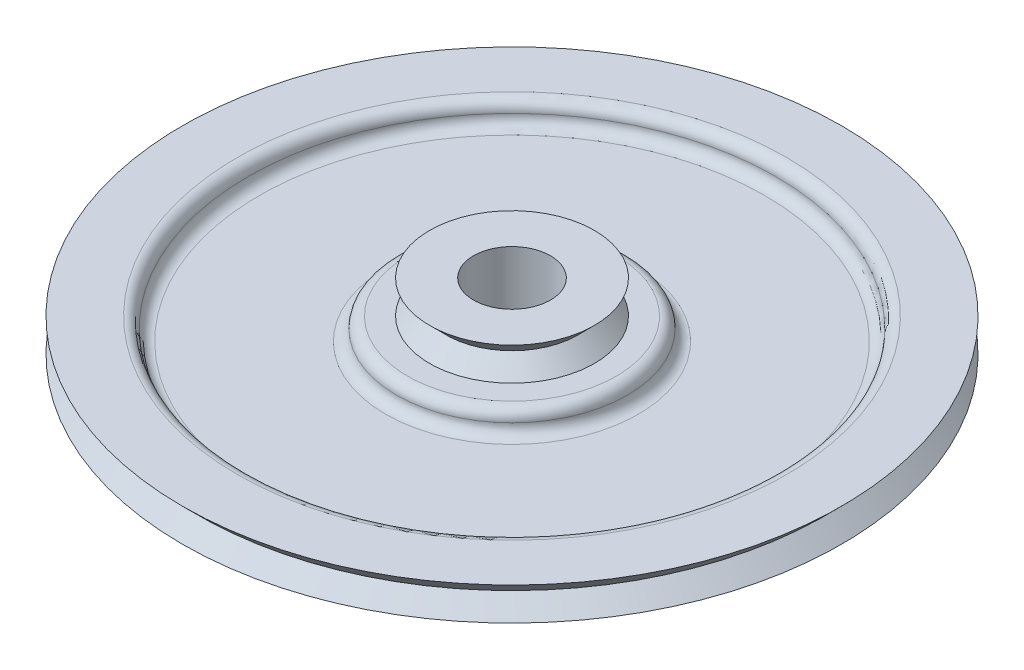
SolidWorks part; units mm, degrees
ref_plane "Front Plane" through (0, 0, 0) normal (0, 0, 1) x (1, 0, 0)
ref_plane "Top Plane" through (0, 0, 0) normal (0, 1, 0) x (1, 0, 0)
ref_plane "Right Plane" through (0, 0, 0) normal (1, 0, 0) x (0, 0, -1)
sketch "Sketch1" plane through (0, 0, 0) normal (0, 0, 1) x (1, 0, 0)
  line L0 (0, 0) -> (0, 13.2622) construction
  line L1 (-3.5, 6) -> (-3.5, 0)
  line L2 (-3.5, 0) -> (-30, 0)
  line L3 (-30, 0) -> (-28.5, 1.5)
  line L4 (-28.5, 1.5) -> (-30, 3)
  line L5 (-30, 3) -> (-7.5, 3)
  line L6 (-7.5, 3) -> (-6, 4.5)
  line L7 (-6, 4.5) -> (-7.5, 6)
  line L8 (-7.5, 6) -> (-3.5, 6)
  point P3 (0, 0)
  dimension "D1" = 3
  dimension "D2" = 7
  dimension "D3" = 15
  dimension "D4" = 60
  dimension "D5" = 45
revolve "Revolve1" add sketch "Sketch1" angle 360 about L0
sketch "Sketch2" plane through (0, 3, 0) normal (0, 1, 0) x (1, 0, 0)
  circle A0 centre (0, 0) radius 10.5
  circle A1 centre (0, 0) radius 24
  circle A2 centre (0, 0) radius 7.5 construction
  circle A3 centre (0, 0) radius 30 construction
  dimension "D1" = 6
  dimension "D2" = 3
extrude "Cut-Extrude1" cut sketch "Sketch2" against normal offset from surface (2 mm away) 1 up to face at (0, 0, -3.5)
fillet "Fillet1" radius 1 4 edges at (0, 3, 10.5) (0, 1, 10.5) (0, 3, 24) (0, 1, 24)
